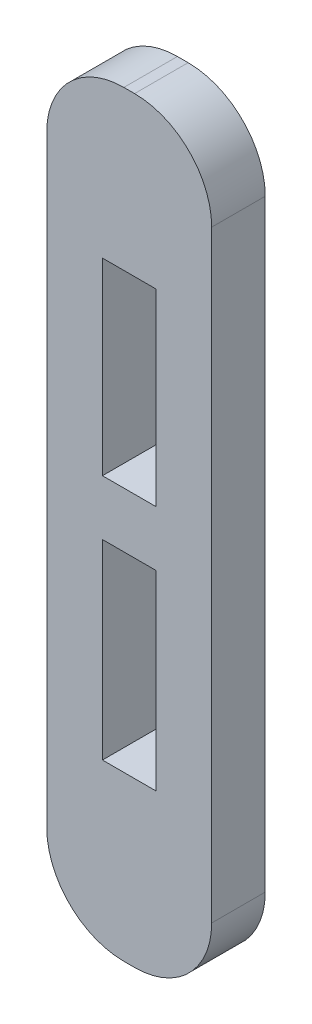
SolidWorks part; units mm, degrees
ref_plane "Front Plane" through (0, 0, 0) normal (0, 0, 1) x (1, 0, 0)
ref_plane "Top Plane" through (0, 0, 0) normal (0, 1, 0) x (1, 0, 0)
ref_plane "Right Plane" through (0, 0, 0) normal (1, 0, 0) x (0, 0, -1)
sketch "Sketch1" plane through (0, 0, 0) normal (0, 0, 1) x (1, 0, 0)
  line L0 (3.2385, 20.7862) -> (1.651, 20.7862) construction
  line L1 (0, 0) -> (4.8895, 0)
  line L2 (0, 0) -> (0, 22.4372)
  line L3 (0, 22.4372) -> (4.8895, 22.4372)
  line L4 (4.8895, 0) -> (4.8895, 22.4372)
  line L7 (3.2385, 17.7382) -> (3.2385, 20.7862) construction
  dimension "D1" = 1.651
  dimension "D2" = 1.651
extrude "Boss-Extrude1" add sketch "Sketch1" along normal blind 1.5875
sketch "Sketch2" plane through (0, 0, 0) normal (0, 0, -1) x (-1, 0, 0)
  line L0 (-1.651, 6.0449) -> (-1.651, 7.3125) construction
  line L1 (-3.2385, 15.1982) -> (-3.2385, 12.1502)
  line L2 (-3.2385, 12.1502) -> (-1.651, 12.1502)
  line L3 (-1.651, 12.1502) -> (-1.651, 15.1982)
  line L5 (-3.2385, 7.3125) -> (-3.2385, 6.0449) construction
  line L6 (-1.651, 17.7382) -> (-1.651, 20.7862) construction
  line L8 (-1.651, 15.1982) -> (-1.651, 16.4682) construction
  line L9 (-3.2385, 16.4682) -> (-3.2385, 15.1982) construction
  line L10 (-3.2385, 17.7382) -> (-1.651, 17.7382) construction
  line L11 (-1.651, 19.5162) -> (-1.651, 16.4682) construction
  line L12 (-3.2385, 19.5162) -> (-3.2385, 16.4682) construction
  line L13 (-1.651, 15.1982) -> (-3.2385, 15.1982) construction
  line L14 (-1.651, 15.1982) -> (-1.651, 16.4682)
  line L15 (-3.2385, 16.4682) -> (-3.2385, 15.1982)
  line L16 (-3.2385, 17.7382) -> (-1.651, 17.7382)
  line L17 (-1.651, 17.7382) -> (-1.651, 16.4682)
  line L18 (-3.2385, 17.7382) -> (-3.2385, 16.4682)
  line L19 (-1.651, 15.1982) -> (-3.2385, 15.1982) construction
  line L20 (-1.651, 6.0449) -> (-1.651, 7.3125)
  line L21 (-3.2385, 7.3125) -> (-3.2385, 6.0449)
  line L22 (-3.2385, 4.8507) -> (-1.651, 4.8507) construction
  line L23 (-1.651, 2.921) -> (-1.651, 6.0449) construction
  line L24 (-3.2385, 2.921) -> (-3.2385, 6.0449) construction
  line L29 (-3.2385, 4.8507) -> (-1.651, 4.8507)
  line L30 (-1.651, 4.8507) -> (-1.651, 6.0449)
  line L31 (-3.2385, 4.8507) -> (-3.2385, 6.0449)
  line L33 (-3.2385, 7.3125) -> (-3.2385, 10.5122)
  line L34 (-3.2385, 10.5122) -> (-1.651, 10.5122)
  line L35 (-1.651, 10.5122) -> (-1.651, 7.3125)
  line L36 (-1.651, 4.8507) -> (-1.651, 1.651) construction
extrude "Cut-Extrude1" cut sketch "Sketch2" against normal through all
fillet "Fillet1" radius 2.286 4 edges at (0, 0, 0.7937) (4.8895, 0, 0.7937) (4.8895, 22.4372, 0.7937) (0, 22.4372, 0.7937)
